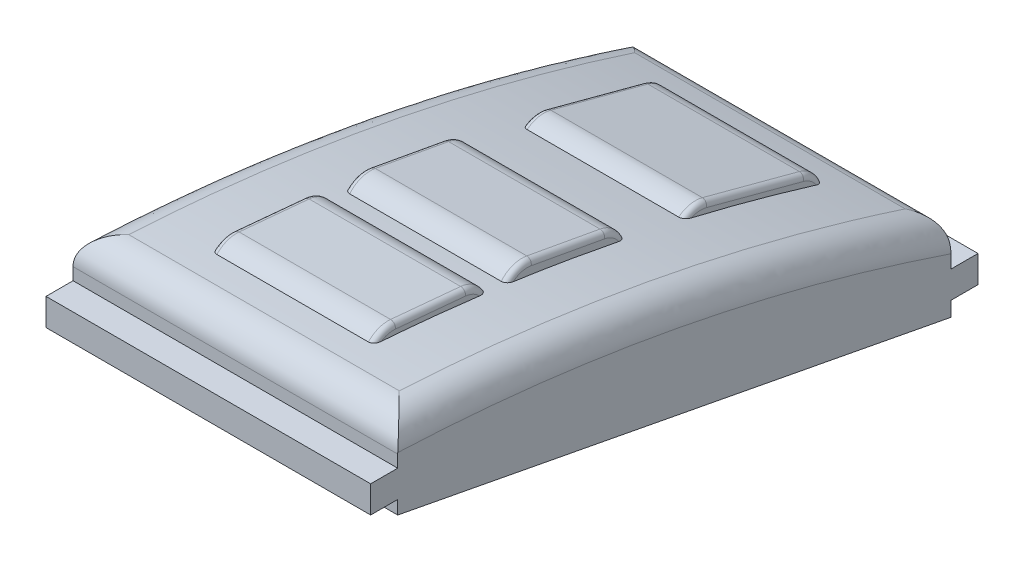
SolidWorks part; units mm, degrees
ref_plane "Front Plane" through (0, 0, 0) normal (0, 0, 1) x (1, 0, 0)
ref_plane "Top Plane" through (0, 0, 0) normal (0, 1, 0) x (1, 0, 0)
ref_plane "Right Plane" through (0, 0, 0) normal (1, 0, 0) x (0, 0, -1)
sketch "Sketch1" plane through (0, 0, 0) normal (1, 0, 0) x (0, 0, -1)
  line L2 (48, 67.0866) -> (48, 68.0866)
  line L4 (68.448, 64.2793) -> (68.448, 63.2793)
  line L6 (48, 67.0866) -> (48, 65.0855)
  line L7 (48, 65.0855) -> (68.448, 61.1913)
  line L8 (68.448, 61.1913) -> (68.448, 63.2793)
  spline S0 degree 2 poles (48, 68.0866) (58.3909, 67.6596) (68.448, 64.2793) knots 0 0 0 1 1 1
  dimension "D1" = 20.448
  dimension "D2" = 2.0011
  dimension "D3" = 2.088
  dimension "D4" = 1
  dimension "D5" = 3.8943
  dimension "D6" = 1
extrude "Boss-Extrude1" add sketch "Sketch1" against normal blind 12
fillet "Fillet1" radius 1 4 edges at (-6, 68.0866, -48) (-6, 64.2793, -68.448)
sketch "Sketch2" plane through (0, 0, 0) normal (1, 0, 0) x (0, 0, -1)
  line L0 (48, 66.0861) -> (48, 66.5861)
  line L2 (48, 66.5861) -> (47, 66.5861)
  line L3 (47, 66.5861) -> (47, 65.5861)
  line L4 (47, 65.5861) -> (48, 65.5861)
  line L6 (48, 65.5861) -> (48, 66.0861)
  line L7 (68.448, 62.2353) -> (68.448, 62.7353)
  line L10 (68.448, 62.7353) -> (69.448, 62.7353)
  line L11 (69.448, 62.7353) -> (69.448, 61.7353)
  line L12 (69.448, 61.7353) -> (68.448, 61.7353)
  line L13 (68.448, 61.7353) -> (68.448, 62.2353)
  dimension "D1" = 0.5
  dimension "D2" = 0.5
  dimension "D3" = 1
  dimension "D4" = 0.5
  dimension "D5" = 1
  dimension "D6" = 0.5
extrude "Boss-Extrude2" add sketch "Sketch2" against normal up to surface (12 mm away) up to face at (-12, 64.8814, -56.1593)
ref_plane "Plane1" through (-6, 0, 0) normal (1, 0, 0) x (0, 0, -1)
sketch "Sketch3" plane through (-6, 0, 0) normal (1, 0, 0) x (0, 0, -1)
  line L0 (50.1155, 67.9689) -> (50.1155, 68.3556)
  line L1 (50.1155, 68.3556) -> (54.2949, 67.9689)
  line L2 (54.2949, 67.9689) -> (54.2949, 67.553)
  line L3 (54.2949, 67.553) -> (54.2949, 67.1655)
  line L4 (54.2949, 67.1655) -> (50.1155, 67.1655)
  line L5 (50.1155, 67.1655) -> (50.1155, 67.9689)
  line L6 (55.024, 67.1655) -> (55.024, 67.9689)
  line L7 (55.024, 67.9689) -> (59.421, 67.1655)
  line L8 (59.421, 67.1655) -> (59.421, 66.1339)
  line L9 (59.421, 66.1339) -> (55.024, 67.1655)
  line L10 (61.5826, 66.2337) -> (61.5826, 66.6497)
  line L11 (61.5826, 66.6497) -> (66.7268, 65.277)
  line L12 (66.7268, 65.277) -> (66.7268, 64.6231)
  line L13 (66.7268, 64.6231) -> (61.5826, 65.563)
  line L14 (61.5826, 65.563) -> (61.5826, 66.2337)
  parabola Q0 (49.0556, 68.0356) -> (67.7576, 64.5077) focus (49.1072, 31.7136) apex (53.1746, 67.6885) construction
  parabola Q1 (49.0556, 68.0356) -> (67.7576, 64.5077) focus (49.1072, 31.7136) apex (53.1746, 67.6885) construction
  parabola Q2 (49.0556, 68.0356) -> (67.7576, 64.5077) focus (49.1072, 31.7136) apex (53.1746, 67.6885) construction
extrude "Boss-Extrude3" add sketch "Sketch3" along normal blind 3 and the other way blind 3
fillet "Fillet2" radius 1 6 edges at (-6, 65.277, -66.7268) (-6, 66.6497, -61.5826) (-6, 67.1655, -59.421) (-6, 67.9689, -55.024) (-6, 67.9689, -54.2949) (-6, 68.3556, -50.1155)
fillet "Fillet3" radius 0.2 18 edges at (-9, 65.2306, -66.4623) (-9, 66.4285, -62.0001) (-3, 65.2306, -66.4623) (-3, 66.4285, -62.0001) (-9, 67.097, -59.1254) (-9, 67.7531, -55.4509) (-3, 67.097, -59.1254) (-3, 67.7531, -55.4509) (-9, 67.889, -53.9692) (-9, 68.2191, -50.4899) (-3, 67.889, -53.9692) (-3, 68.2191, -50.4899) (-9, 65.9372, -64.2529) (-3, 65.9372, -64.2529) (-9, 67.5486, -57.3243) (-3, 67.5486, -57.3243) (-9, 68.1598, -52.2312) (-3, 68.1598, -52.2312)
